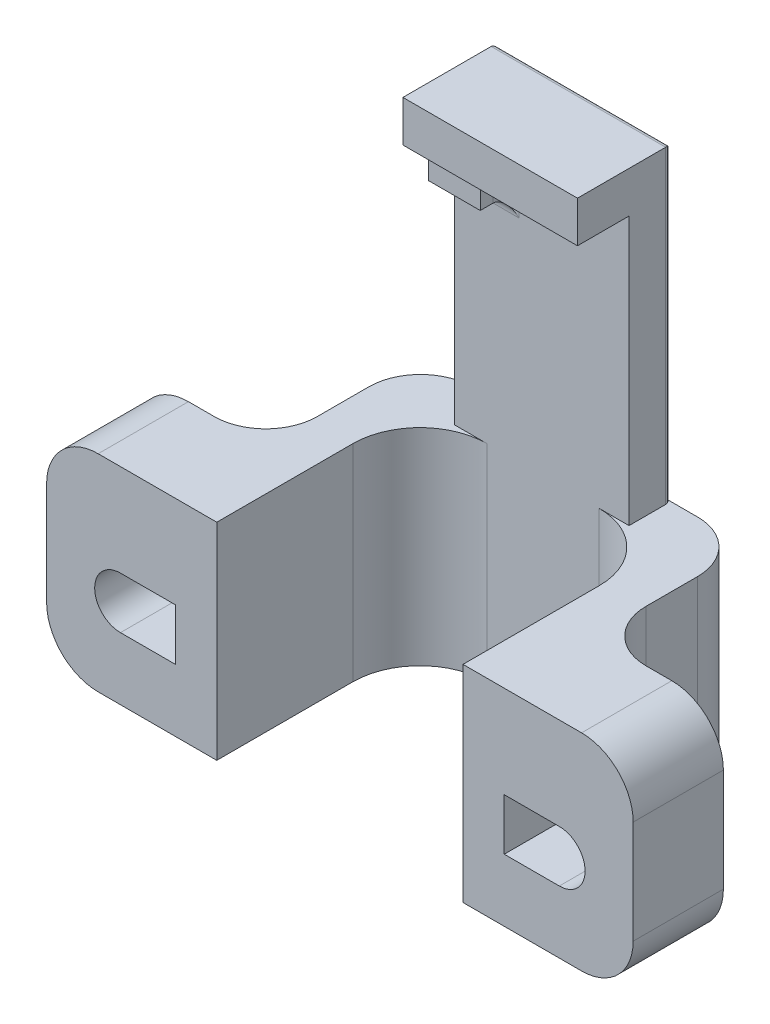
SolidWorks part; units mm, degrees
ref_plane "Front Plane" through (0, 0, 0) normal (0, 0, 1) x (1, 0, 0)
ref_plane "Top Plane" through (0, 0, 0) normal (0, 1, 0) x (1, 0, 0)
ref_plane "Right Plane" through (0, 0, 0) normal (1, 0, 0) x (0, 0, -1)
sketch "Sketch1" plane through (0, 0, 0) normal (0, 0, 1) x (1, 0, 0)
  line L1 (0, 0) -> (12.1285, 0)
  line L2 (0, 0) -> (0, 10.16)
  line L3 (0, 10.16) -> (1.7018, 10.16)
  line L4 (12.1285, 0) -> (12.1285, 10.16)
  line L6 (1.7018, 10.16) -> (1.7018, 25.4)
  line L7 (10.2997, 10.16) -> (10.2997, 25.4)
  line L8 (10.2997, 10.16) -> (12.1285, 10.16)
  line L9 (1.7018, 25.4) -> (10.2997, 25.4)
  dimension "D1" = 12.1285
  dimension "D2" = 10.16
  dimension "D7" = 1.7018
  dimension "D8" = 1.8288
  dimension "D9" = 15.24
  dimension "D10" = 15.24
extrude "Boss-Extrude1" add sketch "Sketch1" along normal blind 2.0574
sketch "Sketch4" plane through (12.1285, 0, 0) normal (1, 0, 0) x (0, 0, -1)
  line L1 (0, 0) -> (-12.065, 0)
  line L2 (0, 0) -> (0, 10.16)
  line L3 (0, 10.16) -> (-12.065, 10.16)
  line L4 (-12.065, 0) -> (-12.065, 10.16)
  dimension "D2" = 12.065
extrude "Boss-Extrude2" add sketch "Sketch4" along normal blind 2.032
sketch "Sketch5" plane through (0, 0, 0) normal (-1, 0, 0) x (0, 0, 1)
  line L1 (0, 0) -> (12.065, 0)
  line L2 (0, 0) -> (0, 10.16)
  line L3 (0, 10.16) -> (12.065, 10.16)
  line L4 (12.065, 0) -> (12.065, 10.16)
  dimension "D1" = 12.065
extrude "Boss-Extrude3" add sketch "Sketch5" along normal blind 2.032
sketch "Sketch8" plane through (0, 0, 2.0574) normal (0, 0, 1) x (1, 0, 0)
  line L0 (10.2997, 10.16) -> (10.2997, 25.4) construction
  line L1 (1.7018, 25.4) -> (10.2997, 25.4)
  line L2 (1.7018, 25.4) -> (1.7018, 23.368)
  line L3 (1.7018, 23.368) -> (10.2997, 23.368)
  line L4 (10.2997, 25.4) -> (10.2997, 23.368)
  dimension "D1" = 2.032
extrude "Boss-Extrude4" add sketch "Sketch8" along normal blind 2.54
fillet "Fillet22" radius 3.302 2 edges
sketch "Sketch26" plane through (0, 23.368, 0) normal (0, -1, 0) x (1, 0, 0)
  line L1 (1.7018, 4.5974) -> (10.2997, 4.5974) construction
  line L2 (8.382, 4.5974) -> (1.7018, 4.5974)
  line L3 (8.382, 4.5974) -> (10.2997, 4.5974)
  line L4 (10.2997, 4.5974) -> (10.2997, 2.0574)
  line L5 (10.2997, 2.0574) -> (1.6203, 2.0574)
  line L6 (1.6203, 2.0574) -> (1.7018, 4.5974)
extrude "Cut-Extrude12" cut sketch "Sketch26" along normal up to surface (13.208 mm away) up to face at (-0.1757, 10.16, 5.8469)
sketch "Sketch28" plane through (0, 0, 2.0574) normal (0, 0, 1) x (1, 0, 0)
  line L0 (1.7018, 23.368) -> (1.7018, 10.16) construction
  line L1 (1.7018, 22.479) -> (4.2418, 22.479)
  line L2 (1.7018, 22.479) -> (1.7018, 21.209)
  line L3 (1.7018, 21.209) -> (4.2418, 21.209)
  line L4 (4.2418, 22.479) -> (4.2418, 21.209)
  line L5 (1.7018, 23.368) -> (10.2997, 23.368) construction
  dimension "D1" = 0.889
  dimension "D2" = 2.54
  dimension "D3" = 1.27
extrude "Boss-Extrude6" add sketch "Sketch28" along normal blind 1.27
sketch "Sketch30" plane through (0, 0, 12.065) normal (0, 0, -1) x (-1, 0, 0)
  line L0 (2.032, 0) -> (5.842, 0)
  line L1 (8.382, 2.54) -> (8.382, 7.62)
  line L2 (5.842, 10.16) -> (2.032, 10.16)
  line L3 (2.032, 0) -> (2.032, 10.16)
  line L4 (4.7449, 3.0766) -> (2.032, 3.0766)
  line L5 (2.032, 3.0766) -> (2.032, 5.6166)
  line L6 (2.032, 5.6166) -> (4.7449, 5.6166)
  arc A0 (5.842, 10.16) -> (8.382, 7.62) centre (5.842, 7.62) cw
  arc A1 (8.382, 2.54) -> (5.842, 0) centre (5.842, 2.54) cw
  arc A2 (4.7449, 3.0766) -> (4.7449, 5.6166) centre (4.7449, 4.3466) ccw
  point P11 (8.382, 0)
  dimension "D2" = 2.54
  dimension "D3" = 2.54
  dimension "D1" = 6.35
extrude "Boss-Extrude7" add sketch "Sketch30" along normal blind 4.445 contours A2 L4 L3 L0 A1 L1 A0 L2 L6 region at (-2.1518, 1.5383, 12.065)
fillet "Fillet23" radius 0.635 2 edges at (4.2418, 21.844, 2.0574) (2.9718, 21.209, 2.0574)
sketch "Sketch34" plane through (0, 0, 7.62) normal (0, 0, -1) x (-1, 0, 0)
  line L1 (4.7449, 7.0771) -> (2.3802, 5.7118)
  line L2 (2.3802, 5.7118) -> (2.3802, 2.9813)
  line L3 (2.3802, 2.9813) -> (4.7449, 1.6161)
  line L4 (4.7449, 1.6161) -> (7.1096, 2.9813)
  line L5 (7.1096, 2.9813) -> (7.1096, 5.7118)
  line L6 (7.1096, 5.7118) -> (4.7449, 7.0771)
  circle A0 centre (4.7449, 4.3466) radius 2.7305 construction
  dimension "D1" = 5.461
extrude "Cut-Extrude15" cut sketch "Sketch34" against normal blind 1.651
fillet "Fillet25" radius 0.254 3 edges at (6.0007, 25.4, 0) (10.2997, 17.78, 0) (1.7018, 17.78, 0)
ref_plane "Plane2" through (6.0643, 0, 0) normal (1, 0, 0) x (0, 0, -1)
mirror "Mirror7" about plane through (6.0643, 0, 0) normal (1, 0, 0) of "Cut-Extrude15", "Boss-Extrude7"
fillet "Fillet26" radius 2.54 6 edges at (-2.032, 1.5383, 7.62) (-2.032, 7.8883, 7.62) (14.1605, 1.5383, 7.62) (14.1605, 7.8883, 7.62) (-2.032, 5.08, 0) (14.1605, 5.08, 0)
